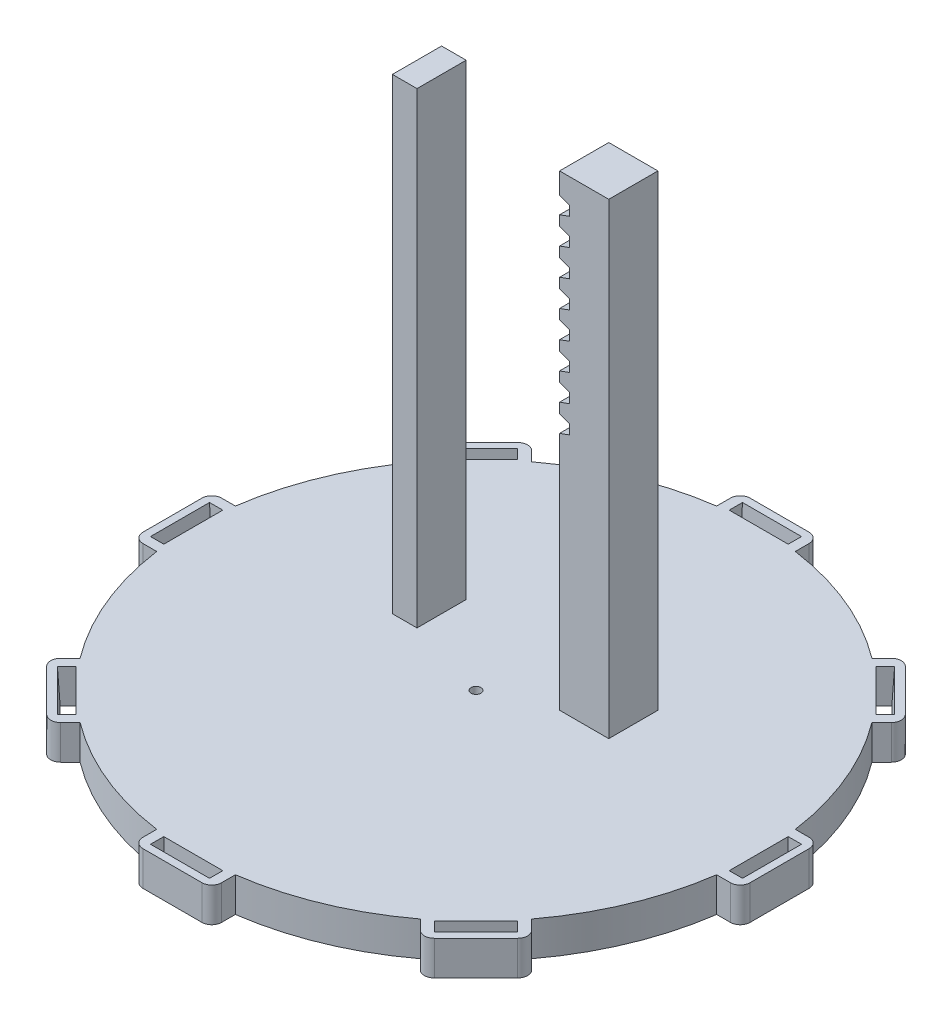
SolidWorks part; units mm, degrees
ref_plane "Front Plane" through (0, 0, 0) normal (0, 0, 1) x (1, 0, 0)
ref_plane "Top Plane" through (0, 0, 0) normal (0, 1, 0) x (1, 0, 0)
ref_plane "Right Plane" through (0, 0, 0) normal (1, 0, 0) x (0, 0, -1)
sketch "Sketch1" plane through (0, 0, 0) normal (0, 1, 0) x (1, 0, 0)
  line L0 (-8, 56.9408) -> (-8, 59.7408)
  line L1 (0, 57.5) -> (0, -57.5) construction
  line L2 (8, 56.9408) -> (8, 59.7408)
  line L3 (-6, 61.7408) -> (6, 61.7408)
  line L4 (39.4147, 47.8999) -> (47.8999, 39.4147)
  line L9 (34.6063, 45.9201) -> (36.5862, 47.8999)
  line L10 (45.9201, 34.6063) -> (47.8999, 36.5862)
  line L15 (61.7408, 6) -> (61.7408, -6)
  line L16 (56.9408, 8) -> (59.7408, 8)
  line L17 (56.9408, -8) -> (59.7408, -8)
  line L22 (47.8999, -39.4147) -> (39.4147, -47.8999)
  line L23 (45.9201, -34.6063) -> (47.8999, -36.5862)
  line L24 (34.6063, -45.9201) -> (36.5862, -47.8999)
  line L29 (6, -61.7408) -> (-6, -61.7408)
  line L30 (8, -56.9408) -> (8, -59.7408)
  line L31 (-8, -56.9408) -> (-8, -59.7408)
  line L36 (-39.4147, -47.8999) -> (-47.8999, -39.4147)
  line L37 (-34.6063, -45.9201) -> (-36.5862, -47.8999)
  line L38 (-45.9201, -34.6063) -> (-47.8999, -36.5862)
  line L43 (-61.7408, -6) -> (-61.7408, 6)
  line L44 (-56.9408, -8) -> (-59.7408, -8)
  line L45 (-56.9408, 8) -> (-59.7408, 8)
  line L50 (-47.8999, 39.4147) -> (-39.4147, 47.8999)
  line L51 (-45.9201, 34.6063) -> (-47.8999, 36.5862)
  line L52 (-34.6063, 45.9201) -> (-36.5862, 47.8999)
  arc A0 (-8, 56.9408) -> (-34.6063, 45.9201) centre (0, 0) ccw
  arc A1 (6, 61.7408) -> (8, 59.7408) centre (6, 59.7408) cw
  arc A2 (-6, 61.7408) -> (-8, 59.7408) centre (-6, 59.7408) ccw
  arc A3 (39.4147, 47.8999) -> (36.5862, 47.8999) centre (38.0005, 46.4857) ccw
  arc A4 (47.8999, 39.4147) -> (47.8999, 36.5862) centre (46.4857, 38.0005) cw
  arc A5 (61.7408, 6) -> (59.7408, 8) centre (59.7408, 6) ccw
  arc A6 (61.7408, -6) -> (59.7408, -8) centre (59.7408, -6) cw
  arc A7 (47.8999, -39.4147) -> (47.8999, -36.5862) centre (46.4857, -38.0005) ccw
  arc A8 (39.4147, -47.8999) -> (36.5862, -47.8999) centre (38.0005, -46.4857) cw
  arc A9 (6, -61.7408) -> (8, -59.7408) centre (6, -59.7408) ccw
  arc A10 (-6, -61.7408) -> (-8, -59.7408) centre (-6, -59.7408) cw
  arc A11 (-39.4147, -47.8999) -> (-36.5862, -47.8999) centre (-38.0005, -46.4857) ccw
  arc A12 (-47.8999, -39.4147) -> (-47.8999, -36.5862) centre (-46.4857, -38.0005) cw
  arc A13 (-61.7408, -6) -> (-59.7408, -8) centre (-59.7408, -6) ccw
  arc A14 (-61.7408, 6) -> (-59.7408, 8) centre (-59.7408, 6) cw
  arc A15 (-47.8999, 39.4147) -> (-47.8999, 36.5862) centre (-46.4857, 38.0005) ccw
  arc A16 (-39.4147, 47.8999) -> (-36.5862, 47.8999) centre (-38.0005, 46.4857) cw
  arc A17 (-45.9201, 34.6063) -> (-56.9408, 8) centre (0, 0) ccw
  arc A18 (-56.9408, -8) -> (-45.9201, -34.6063) centre (0, 0) ccw
  arc A19 (34.6063, 45.9201) -> (8, 56.9408) centre (0, 0) ccw
  arc A20 (-34.6063, -45.9201) -> (-8, -56.9408) centre (0, 0) ccw
  arc A21 (8, -56.9408) -> (34.6063, -45.9201) centre (0, 0) ccw
  arc A22 (45.9201, -34.6063) -> (56.9408, -8) centre (0, 0) ccw
  arc A23 (56.9408, 8) -> (45.9201, 34.6063) centre (0, 0) ccw
  point P11 (8, 61.7408)
  point P14 (-8, 61.7408)
  point P17 (-8, 58.3408)
  point P98 (0, 0)
  dimension "D1" = 115
  dimension "D2" = 2
  dimension "D3" = 16
  dimension "D4" = 2.8
  dimension "D7" = 8
extrude "Boss-Extrude1" add sketch "Sketch1" along normal blind 7
sketch "Sketch2" plane through (0, 7, 0) normal (0, 1, 0) x (1, 0, 0)
  line L0 (-57.5, 0) -> (57.5, 0) construction
  line L1 (0, 0) -> (0, 10) construction
  line L7 (12, 5) -> (22, 5)
  line L14 (0, 10) -> (28.3122, 10) construction
  line L15 (0, 10) -> (-19.5, 10) construction
  line L17 (12, 5) -> (12, 15)
  line L18 (-22, 15) -> (-17, 15)
  line L19 (-22, 15) -> (-22, 5)
  line L20 (-22, 5) -> (-17, 5)
  line L21 (-17, 15) -> (-17, 5)
  line L22 (-22, 15) -> (-17, 5) construction
  line L23 (-22, 5) -> (-17, 15) construction
  line L24 (12, 15) -> (22, 15)
  line L25 (22, 5) -> (22, 15)
  line L26 (12, 5) -> (22, 15) construction
  line L27 (12, 15) -> (22, 5) construction
  circle A0 centre (0, 0) radius 57.5 construction
  point P8 (17, 10)
  dimension "D1" = 10
  dimension "D2" = 29
  dimension "D3" = 12
  dimension "D4" = 10
  dimension "D5" = 10
  dimension "D6" = 5
  dimension "D7" = 10
extrude "Boss-Extrude2" add sketch "Sketch2" along normal blind 95
sketch "Sketch15" plane through (0, 0, 0) normal (0, -1, 0) x (1, 0, 0)
  circle A0 centre (0, 0) radius 1
  dimension "D1" = 2
extrude "Cut-Extrude3" cut sketch "Sketch15" along direction (0, 1, 0) on the side against the normal up to surface (7 mm away) contours A0 up to face at (0, 7, 0)
sketch "Sketch16" plane through (0, 0, 0) normal (0, -1, 0) x (1, 0, 0)
  line L1 (-6, 59.8) -> (6, 59.8)
  line L2 (-6, 59.8) -> (-6, 57.5)
  line L3 (-6, 57.5) -> (6, 57.5)
  line L4 (6, 59.8) -> (6, 57.5)
  point P5 (0, 57.5)
  dimension "D1" = 2.3
  dimension "D2" = 12
  dimension "D3" = 57.5
sketch "Sketch17" plane through (0, 7, 0) normal (0, 1, 0) x (1, 0, 0)
  line L0 (-6, -57.5) -> (6, -57.5) construction
  line L1 (-6, -57.5) -> (6, -57.5)
  line L2 (-6, -57.5) -> (-6, -60.2)
  line L3 (-6, -60.2) -> (6, -60.2)
  line L4 (6, -60.2) -> (6, -57.5)
  dimension "D1" = 2.7
ref_axis "Axis1" through (0, 107.1, 0) along (0, -1, 0)
loft "Cut-Loft2" cut profiles "Sketch16", "Sketch17"
pattern_circular "CirPattern1" count 8 over 360 about axis through (0, 107.1, 0) along (0, -1, 0) of "Cut-Loft2"
sketch "Sketch18" plane through (0, 0, -15) normal (0, 0, -1) x (-1, 0, 0)
  line L0 (-12, 97.7279) -> (-14, 97)
  line L1 (-12, 102) -> (-12, 7) construction
  line L2 (-14, 97) -> (-14, 95)
  line L3 (-14, 96) -> (-15.9044, 96) construction
  line L4 (-12, 97.7279) -> (-12, 94.2721)
  line L5 (-12, 94.2721) -> (-14, 95)
  line L6 (-22, 102) -> (-12, 102) construction
  point P9 (-12, 96)
  dimension "D1" = 5
  dimension "D2" = 110
  dimension "D3" = 2
  dimension "D4" = 2
extrude "Cut-Extrude4" cut sketch "Sketch18" against normal blind 10
pattern_linear "LPattern1" count 8 spacing 5.5 along (0, -1, 0) of "Cut-Extrude4"
equation "\"85.00.00mm\"=8500"
